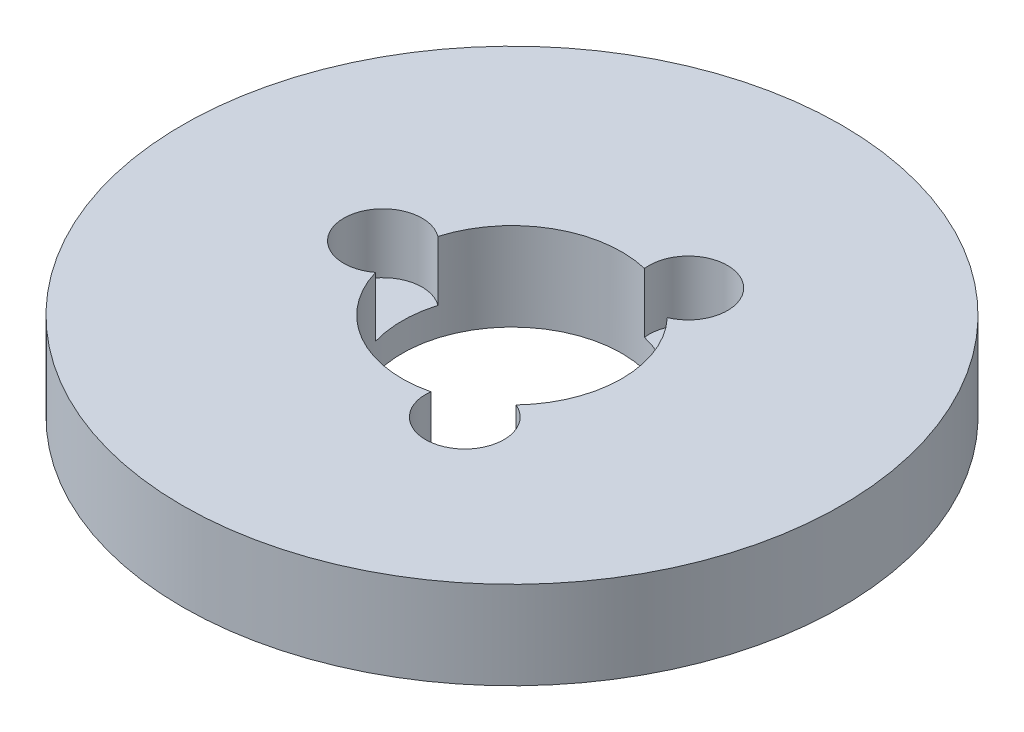
SolidWorks part; units mm, degrees
ref_plane "Front Plane" through (0, 0, 0) normal (0, 0, 1) x (1, 0, 0)
ref_plane "Top Plane" through (0, 0, 0) normal (0, 1, 0) x (1, 0, 0)
ref_plane "Right Plane" through (0, 0, 0) normal (1, 0, 0) x (0, 0, -1)
sketch "Sketch1" plane through (0, 0, 0) normal (0, 1, 0) x (1, 0, 0)
  circle A0 centre (0, 0) radius 67.5
  dimension "FLANGE_OD" = 135
extrude "Boss-Extrude1" add sketch "Sketch1" along normal blind 18
sketch "Sketch2" plane through (0, 0, 0) normal (0, 1, 0) x (1, 0, 0)
  circle A0 centre (0, 0) radius 22.5
  dimension "BORE_D" = 45
extrude "Cut-Extrude1" cut sketch "Sketch2" along normal through all
sketch "Sketch3" plane through (0, 18, 0) normal (0, 1, 0) x (1, 0, 0)
  circle A0 centre (0, 0) radius 26.4345 construction
  circle A1 centre (-26.4345, 0) radius 8.025
  dimension "BOLT_D" = 16.05
  dimension "BOLT_PCD" = 52.8689
extrude "Cut-Extrude2" cut sketch "Sketch3" against normal blind 12.2285
pattern_circular "CirPattern1" count 3 over 360 about axis through (0, 0, 0) along (0, 1, 0) of "Cut-Extrude2"
